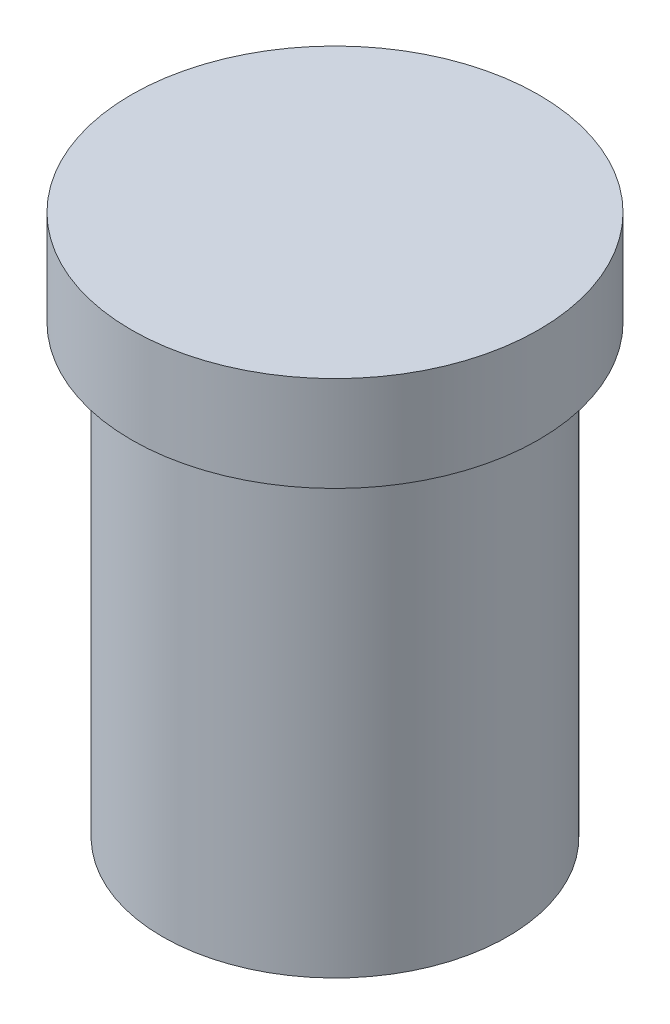
SolidWorks part; units mm, degrees
ref_plane "Front" through (0, 0, 0) normal (0, 0, 1) x (1, 0, 0)
ref_plane "Top" through (0, 0, 0) normal (0, 1, 0) x (1, 0, 0)
ref_plane "Right" through (0, 0, 0) normal (1, 0, 0) x (0, 0, -1)
sketch "Esboço1" plane through (0, 0, 0) normal (0, 1, 0) x (1, 0, 0)
  circle A0 centre (0, 0) radius 6.85
  point P2 (0, 0)
  point P4 (0, 0)
  dimension "D1" = 13.7
extrude "Ressalto-extrusão1" add sketch "Esboço1" along normal blind 3.2
sketch "Esboço3" plane through (0, 0, 0) normal (0, -1, 0) x (1, 0, 0)
  circle A0 centre (0, 0) radius 5.8
  point P2 (0, 0)
  dimension "D1" = 11.6
extrude "Ressalto-extrusão2" add sketch "Esboço3" along normal blind 15
sketch "Esboço4" plane through (0, -15, 0) normal (0, -1, 0) x (1, 0, 0)
extrude "Ressalto-extrusão3" add sketch "Esboço3<2>" along normal blind 15
sketch "Esboço3<2>" plane through (0, 0, 0) normal (0, -1, 0) x (1, 0, 0) same geometry as "Esboço3"
